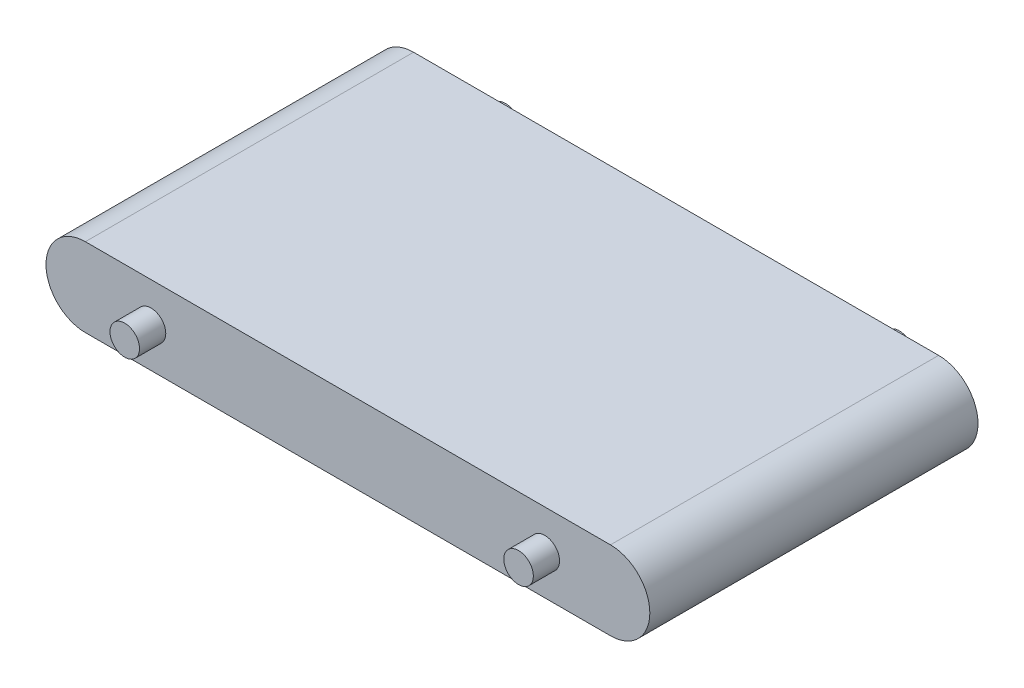
SolidWorks part; units mm, degrees
ref_plane "Front Plane" through (0, 0, 0) normal (0, 0, 1) x (1, 0, 0)
ref_plane "Top Plane" through (0, 0, 0) normal (0, 1, 0) x (1, 0, 0)
ref_plane "Right Plane" through (0, 0, 0) normal (1, 0, 0) x (0, 0, -1)
sketch "Sketch2" plane through (0, 0, 0) normal (0, 0, 1) x (1, 0, 0)
  line L1 (-230, 30) -> (230, 30)
  line L2 (-230, 30) -> (-230, -30)
  line L3 (-230, -30) -> (230, -30)
  line L4 (230, 30) -> (230, -30)
  line L5 (-230, 30) -> (230, -30) construction
  line L6 (-230, -30) -> (230, 30) construction
  point P0 (0, 0)
  dimension "D1" = 460
  dimension "D2" = 60
extrude "Boss-Extrude1" add sketch "Sketch2" along normal mid plane 250
fillet "Fillet1" 2 edges at (-230, 30, 0) (-230, -30, 0) type full round first side face at (0, 30, 0) second side face at (0, -30, 0) middle face at (-230, 0, 0)
fillet "Fillet2" 2 edges at (230, 30, 0) (230, -30, 0) type full round first side face at (15, 30, 0) second side face at (15, -30, 0) middle face at (230, 0, 0)
sketch "Sketch3" plane through (0, 0, 125) normal (0, 0, 1) x (1, 0, 0)
  circle A0 centre (-150, 0) radius 11.25
  circle A1 centre (150, 0) radius 11.25
  arc A2 (-200, 30) -> (-200, -30) centre (-200, 0) ccw construction
  arc A3 (200, -30) -> (200, 30) centre (200, 0) ccw construction
  dimension "D1" = 22.5
  dimension "D2" = 50
  dimension "D3" = 50
extrude "Boss-Extrude2" add sketch "Sketch3" along normal blind 20
mirror "Mirror1" about plane through (0, 0, 0) normal (0, 0, 1) of "Boss-Extrude2"
